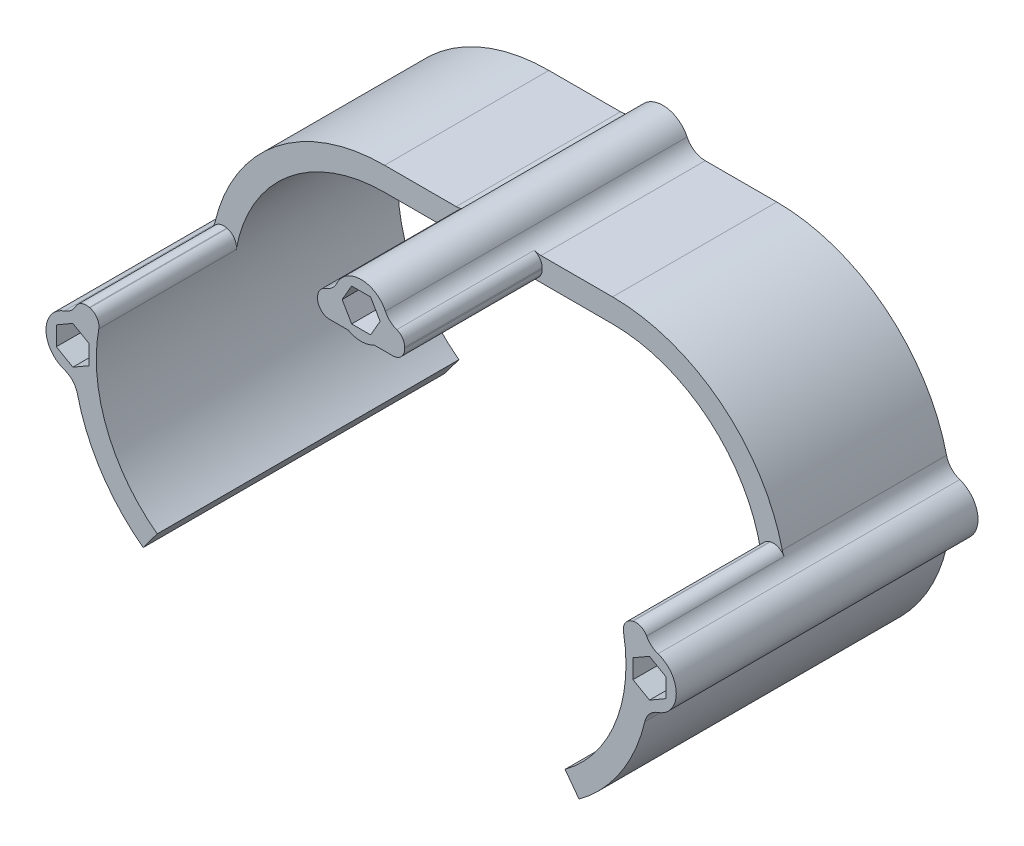
SolidWorks part; units mm, degrees
ref_plane "前视基准面" through (0, 0, 0) normal (0, 0, 1) x (1, 0, 0)
ref_plane "上视基准面" through (0, 0, 0) normal (0, 1, 0) x (1, 0, 0)
ref_plane "右视基准面" through (0, 0, 0) normal (1, 0, 0) x (0, 0, -1)
sketch "草图2" plane through (0, 0, 0) normal (0, 0, 1) x (1, 0, 0)
  line L0 (-17, 26) -> (-6.3246, 26)
  line L1 (0, 0) -> (0, 26) construction
  line L2 (-17, 22.5) -> (-1.9365, 22.5)
  line L3 (-30.4135, -18.0646) -> (-32.5, -20.8746)
  line L4 (30.4135, -18.0646) -> (32.5, -20.8746)
  line L5 (6.3246, 26) -> (17, 26)
  line L6 (-17, 26) -> (17, 26) construction
  line L7 (1.9365, 22.5) -> (17, 22.5)
  line L8 (1.4145, 28.45) -> (-1.4145, 28.45)
  line L9 (-1.4145, 28.45) -> (-2.829, 26)
  line L10 (-2.829, 26) -> (-1.4145, 23.55)
  line L11 (-1.4145, 23.55) -> (1.4145, 23.55)
  line L12 (1.4145, 23.55) -> (2.829, 26)
  line L13 (2.829, 26) -> (1.4145, 28.45)
  line L14 (-17, 22.5) -> (17, 22.5) construction
  line L15 (-43, -2.829) -> (-45.45, -1.4145)
  line L16 (45.45, -1.4145) -> (45.45, 1.4145)
  line L17 (45.45, 1.4145) -> (43, 2.829)
  line L18 (43, 2.829) -> (40.55, 1.4145)
  line L19 (40.55, 1.4145) -> (40.55, -1.4145)
  line L20 (40.55, -1.4145) -> (43, -2.829)
  line L21 (43, -2.829) -> (45.45, -1.4145)
  line L22 (-40.55, -1.4145) -> (-43, -2.829)
  line L23 (-40.55, 1.4145) -> (-40.55, -1.4145)
  line L24 (-43, 2.829) -> (-40.55, 1.4145)
  line L25 (-45.45, 1.4145) -> (-43, 2.829)
  line L26 (-45.45, -1.4145) -> (-45.45, 1.4145)
  arc A0 (-17, 26) -> (-42.3103, 5.9487) centre (-17, 0) ccw
  arc A1 (17, 26) -> (42.3103, 5.9487) centre (17, 0) cw
  arc A2 (17, 22.5) -> (30.4135, -18.0646) centre (17, 0) cw
  arc A3 (-17, 22.5) -> (-30.4135, -18.0646) centre (-17, 0) ccw
  arc A5 (-3.614, 27.7143) -> (3.614, 27.7143) centre (0, 26) cw
  circle A6 centre (0, 26) radius 2.45 construction
  arc A7 (-1.9365, 22.5) -> (1.9365, 22.5) centre (0, 26) ccw
  circle A8 centre (43, 0) radius 2.45 construction
  arc A9 (44.2747, 3.7914) -> (44.2747, -3.7914) centre (43, 0) cw
  arc A10 (42.3103, -5.9487) -> (32.5, -20.8746) centre (17, 0) cw
  arc A11 (17, 26) -> (32.5, -20.8746) centre (17, 0) cw construction
  arc A12 (-44.2747, 3.7914) -> (-44.2747, -3.7914) centre (-43, 0) ccw
  arc A13 (-42.3103, -5.9487) -> (-32.5, -20.8746) centre (-17, 0) ccw
  arc A14 (-17, 26) -> (-32.5, -20.8746) centre (-17, 0) ccw construction
  arc A15 (3.614, 27.7143) -> (6.3246, 26) centre (6.3246, 29) ccw
  arc A16 (-3.614, 27.7143) -> (-6.3246, 26) centre (-6.3246, 29) cw
  arc A17 (-44.2747, -3.7914) -> (-42.3103, -5.9487) centre (-45.2308, -6.635) cw
  arc A18 (-44.2747, 3.7914) -> (-42.3103, 5.9487) centre (-45.2308, 6.635) ccw
  arc A19 (44.2747, -3.7914) -> (42.3103, -5.9487) centre (45.2308, -6.635) ccw
  arc A20 (44.2747, 3.7914) -> (42.3103, 5.9487) centre (45.2308, 6.635) cw
  point P48 (4, 26)
  point P51 (-4, 26)
  point P54 (-42.6923, -3.9881)
  point P57 (-42.6923, 3.9881)
  point P60 (42.6923, -3.9881)
  point P63 (42.6923, 3.9881)
  dimension "D2" = 26
  dimension "D5" = 4
  dimension "D7" = 4
  dimension "D9" = 4
  dimension "D10" = 3
  dimension "D11" = 3
  dimension "D12" = 3
  dimension "D1" = 34
  dimension "D3" = 65
  dimension "D6" = 4.9
  dimension "D8" = 4.9
  dimension "D4" = 3.5
extrude "凸台-拉伸1" add sketch "草图2" along normal blind 45
sketch "草图3" plane through (0, 0, 45) normal (0, 0, 1) x (1, 0, 0)
  line L0 (-42.161, 6.5516) -> (-38.774, 5.6696)
  line L1 (-38.774, 5.6696) -> (-17, 0) construction
  line L2 (-32.5, -20.8746) -> (-30.4135, -18.0646) construction
  line L3 (42.161, 6.5516) -> (38.774, 5.6696)
  line L4 (38.774, 5.6696) -> (17, 0) construction
  line L5 (30.4135, -18.0646) -> (32.5, -20.8746) construction
  line L6 (-32.5, -20.8746) -> (-30.4135, -18.0646)
  line L7 (-17, 22.5) -> (-1.9365, 22.5)
  line L8 (1.9365, 22.5) -> (17, 22.5)
  line L9 (30.4135, -18.0646) -> (32.5, -20.8746)
  line L10 (17, 26) -> (6.3246, 26)
  line L11 (-6.3246, 26) -> (-17, 26)
  line L13 (-17, 22.5) -> (-6.5, 22.5)
  line L14 (6.5, 22.5) -> (17, 22.5)
  line L16 (17, 26) -> (6.5, 26)
  line L17 (-6.5, 26) -> (-17, 26)
  line L18 (-6.5, 26) -> (-6.5, 22.5)
  line L19 (6.5, 22.5) -> (6.5, 26)
  line L20 (0, 30) -> (0, 0) construction
  arc A0 (3.614, 27.7143) -> (-3.614, 27.7143) centre (0, 26) ccw construction
  arc A16 (-17, 26) -> (-42.3103, 5.9487) centre (-17, 0) ccw
  arc A17 (-44.2747, 3.7914) -> (-42.3103, 5.9487) centre (-45.2308, 6.635) ccw
  arc A18 (-44.2747, 3.7914) -> (-44.2747, -3.7914) centre (-43, 0) ccw
  arc A19 (-42.3103, -5.9487) -> (-44.2747, -3.7914) centre (-45.2308, -6.635) ccw
  arc A20 (-42.3103, -5.9487) -> (-32.5, -20.8746) centre (-17, 0) ccw
  arc A21 (-17, 22.5) -> (-30.4135, -18.0646) centre (-17, 0) ccw
  arc A22 (-1.9365, 22.5) -> (1.9365, 22.5) centre (0, 26) ccw
  arc A23 (30.4135, -18.0646) -> (17, 22.5) centre (17, 0) ccw
  arc A24 (32.5, -20.8746) -> (42.3103, -5.9487) centre (17, 0) ccw
  arc A25 (44.2747, -3.7914) -> (42.3103, -5.9487) centre (45.2308, -6.635) ccw
  arc A26 (44.2747, -3.7914) -> (44.2747, 3.7914) centre (43, 0) ccw
  arc A27 (42.3103, 5.9487) -> (44.2747, 3.7914) centre (45.2308, 6.635) ccw
  arc A28 (42.3103, 5.9487) -> (17, 26) centre (17, 0) ccw
  arc A29 (3.614, 27.7143) -> (6.3246, 26) centre (6.3246, 29) ccw
  arc A30 (3.614, 27.7143) -> (-3.614, 27.7143) centre (0, 26) ccw
  arc A31 (-6.3246, 26) -> (-3.614, 27.7143) centre (-6.3246, 29) ccw
  arc A32 (-17, 26) -> (-42.161, 6.5516) centre (-17, 0) ccw
  arc A37 (-17, 22.5) -> (-38.774, 5.6696) centre (-17, 0) ccw
  arc A39 (38.774, 5.6696) -> (17, 22.5) centre (17, 0) ccw
  arc A44 (42.161, 6.5516) -> (17, 26) centre (17, 0) ccw
  dimension "D2" = 68
  dimension "D3" = 68
  dimension "D4" = 13
  dimension "D1" = 0
extrude "切除-拉伸1" cut sketch "草图3" against normal blind 20.5
fillet "圆角1" radius 1.8 8 edges at (-6.5, 22.5, 34.75) (-6.5, 26, 34.75) (6.5, 22.5, 34.75) (6.5, 26, 34.75) (38.774, 5.6696, 34.75) (42.161, 6.5516, 34.75) (-38.774, 5.6696, 34.75) (-42.161, 6.5516, 34.75)
